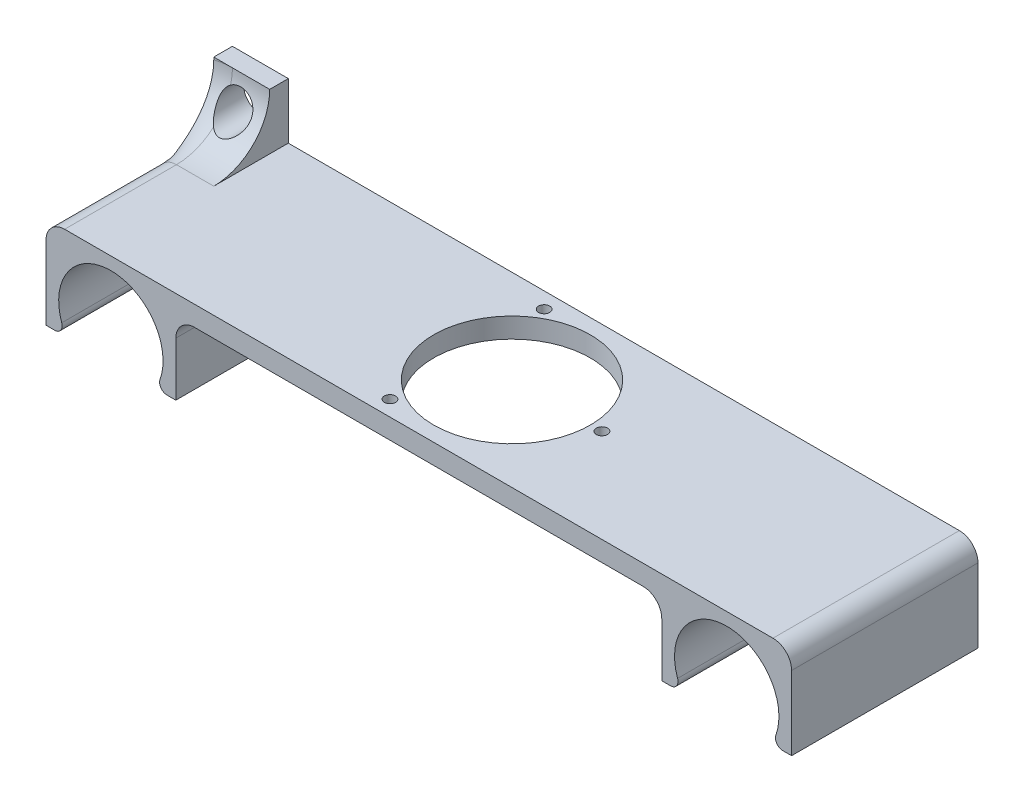
SolidWorks part; units mm, degrees
ref_plane "Front Plane" through (0, 0, 0) normal (0, 0, 1) x (1, 0, 0)
ref_plane "Top Plane" through (0, 0, 0) normal (0, 1, 0) x (1, 0, 0)
ref_plane "Right Plane" through (0, 0, 0) normal (1, 0, 0) x (0, 0, -1)
sketch "Sketch1" plane through (0, 0, 0) normal (0, 0, 1) x (1, 0, 0)
  line L1 (-50, 17.4) -> (-15.2, 17.4)
  line L2 (-50, 17.4) -> (-50, -17.4)
  line L5 (50, 12.0226) -> (-15.1728, 12.0226)
  line L6 (-50, -17.4) -> (-15.2, 17.4) construction
  line L7 (-15.2, 17.4) -> (50, 17.4)
  line L9 (50, 17.4) -> (50, 12.0226)
  line L16 (-15.1728, 12.0226) -> (-15.1728, -17.4)
  line L17 (-15.1728, -17.4) -> (-50, -17.4)
  circle A0 centre (-32.6, 0) radius 14
  point P6 (-32.6, 17.4)
  dimension "D1" = 28
  dimension "D3" = 34.8
  dimension "D5" = 100
extrude "Boss-Extrude1" add sketch "Sketch1" along normal blind 50
mirror "Mirror1" about plane through (50, 17.4, 50) normal (-1, 0, 0) of "Boss-Extrude1"
sketch "Sketch2" plane through (0, 17.4, 0) normal (0, 1, 0) x (1, 0, 0)
  line L0 (-50, 0) -> (150, -50) construction
  line L3 (-50, -50) -> (150, 0) construction
  circle A0 centre (50, -25) radius 21
  point P6 (50, -22.5)
  dimension "D1" = 42
extrude "Cut-Extrude1" cut sketch "Sketch2" against normal blind 45
sketch "Sketch3" plane through (0, 17.4, 0) normal (0, 1, 0) x (1, 0, 0)
  circle A0 centre (50, -25) radius 24.0023 construction
  circle A1 centre (50, -25) radius 21 construction
  circle A2 centre (37.8958, -4.2733) radius 1.5
  circle A3 centre (74.002, -24.8808) radius 1.5
  circle A4 centre (38.1023, -45.8459) radius 1.5
  point P6 (38.1023, -4)
  point P13 (50, -25)
  dimension "D1" = 3.0023
  dimension "D2" = 3
  dimension "D3" = 3
extrude "Cut-Extrude2" cut sketch "Sketch3" against normal blind 45
sketch "Sketch4" plane through (0, 0, 0) normal (0, 0, -1) x (-1, 0, 0)
  line L1 (35, 32.4) -> (50, 32.4)
  line L2 (35, 32.4) -> (35, 17.4)
  line L3 (35, 17.4) -> (50, 17.4)
  line L4 (50, 32.4) -> (50, 17.4)
  line L5 (35, 32.4) -> (50, 17.4) construction
  line L6 (35, 17.4) -> (50, 32.4) construction
  point P0 (42.5, 24.9)
  dimension "D1" = 15
  dimension "D2" = 15
extrude "Boss-Extrude2" add sketch "Sketch4" against normal blind 5
sketch "Sketch5" plane through (0, 0, 0) normal (0, 0, -1) x (-1, 0, 0)
  line L0 (35, 17.4) -> (50, 32.4) construction
  line L1 (50, 32.4) -> (50, -17.4) construction
  line L2 (50, 32.4) -> (35, 32.4) construction
  circle A0 centre (42.5, 24.9) radius 4.5
  dimension "D1" = 9
extrude "Cut-Extrude3" cut sketch "Sketch5" against normal blind 5
fillet "Fillet1" radius 5 8 edges at (115.1728, -17.4, 25) (150, 17.4, 25) (150, -17.4, 25) (-15.1728, -17.4, 25) (-50, -17.4, 25) (-50, 17.4, 27.5) (-15.1728, 12.0226, 25) (115.1728, 12.0226, 25)
fillet "Fillet2" radius 15 2 edges at (-48.5355, 15.9355, 5) (-40, 17.4, 5)
sketch "Sketch7" plane through (0, 0, 0) normal (0, 0, -1) x (-1, 0, 0)
  line L0 (50, 32.4) -> (50, -12.4) construction
  line L1 (50, -7.4) -> (-150, -7.4)
  line L2 (50, -7.4) -> (50, -17.4)
  line L3 (50, -17.4) -> (-150, -17.4)
  line L4 (-150, -7.4) -> (-150, -17.4)
  line L5 (-150, 12.4) -> (-150, -12.4) construction
  line L6 (-145, -17.4) -> (-120.1728, -17.4) construction
  dimension "D1" = 10
extrude "Cut-Extrude4" cut sketch "Sketch7" against normal up to surface (50 mm away) up to face at (50, -1.3443, 50)
fillet "Fillet3" radius 2 4 edges at (144.4844, -7.4, 25) (120.7156, -7.4, 25) (-44.4844, -7.4, 25) (-20.7156, -7.4, 25)
